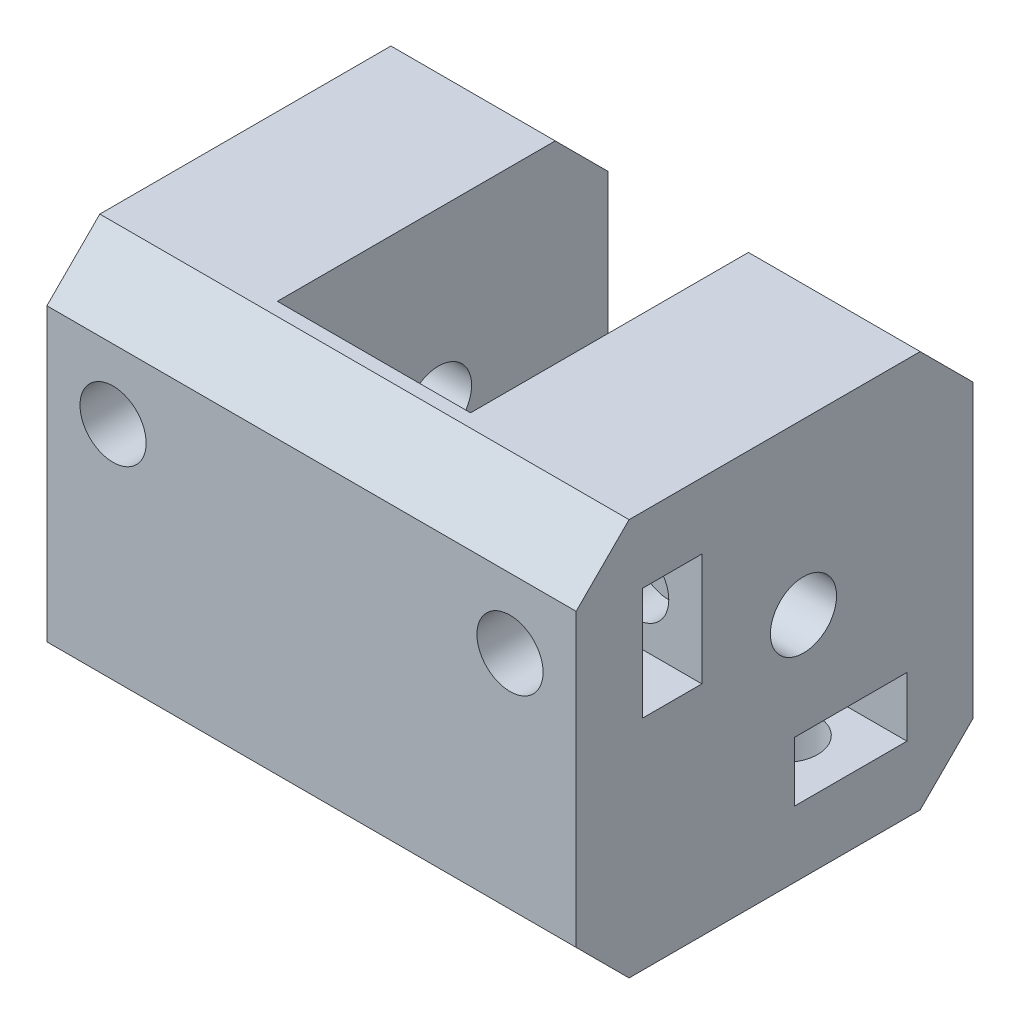
SolidWorks part; units mm, degrees
ref_plane "Front Plane" through (0, 0, 0) normal (0, 0, 1) x (1, 0, 0)
ref_plane "Top Plane" through (0, 0, 0) normal (0, 1, 0) x (1, 0, 0)
ref_plane "Right Plane" through (0, 0, 0) normal (1, 0, 0) x (0, 0, -1)
sketch "Sketch1" plane through (0, 0, 0) normal (0, 0, 1) x (1, 0, 0)
  line L0 (-71.5929, 28.752) -> (-71.5929, 34.452) construction
  line L1 (-31.5929, 27.752) -> (-71.5929, 27.752)
  line L2 (-31.5929, 27.752) -> (-31.5929, 57.752)
  line L3 (-31.5929, 57.752) -> (-71.5929, 57.752)
  line L4 (-71.5929, 27.752) -> (-71.5929, 57.752)
  line L5 (-64.8929, 27.752) -> (-70.5929, 27.752) construction
  line L6 (-31.5929, 34.452) -> (-31.5929, 28.752) construction
  dimension "D1" = 30
extrude "Boss-Extrude1" add sketch "Sketch1" along normal blind 30 contours L3 L4 L1 L2
sketch "Sketch2" plane through (0, 57.752, 0) normal (0, 1, 0) x (1, 0, 0)
  line L0 (-31.5929, 0) -> (-71.5929, 0) construction
  line L1 (-44.5729, -25) -> (-59.1729, -25)
  line L2 (-44.5729, -25) -> (-44.5729, 8.7289)
  line L3 (-44.5729, 8.7289) -> (-59.1729, 8.7289)
  line L4 (-59.1729, -25) -> (-59.1729, 8.7289)
  line L6 (-45.5729, -15.5089) -> (-45.5729, -10.5089) construction
  line L8 (-58.1729, -6.0089) -> (-58.1729, -20.0089) construction
  dimension "D1" = 25
  dimension "D2" = 1
  dimension "D3" = 1
extrude "Cut-Extrude1" cut sketch "Sketch2" against normal offset from surface (25 mm away) 5 up to face at (-51.5929, 27.752, 15)
sketch "Sketch3" plane through (-31.5929, 0, 0) normal (1, 0, 0) x (0, 0, -1)
  line L0 (0, 57.752) -> (-30, 27.752) construction
  line L1 (-30, 57.752) -> (0, 57.752) construction
  line L2 (0, 27.752) -> (0, 57.752) construction
  circle A1 centre (-12.8221, 44.9299) radius 2.5 construction
  circle A2 centre (-12.8221, 44.9299) radius 2.5
  dimension "D1" = 5
extrude "Cut-Extrude2" cut sketch "Sketch3" against normal through all contours A2
sketch "Sketch4" plane through (-31.5929, 0, 0) normal (1, 0, 0) x (0, 0, -1)
  line L0 (0, 57.752) -> (-30, 27.752) construction
  line L1 (-5, 32.752) -> (-13.5, 32.752)
  line L2 (-5, 32.752) -> (-5, 37.252)
  line L3 (-5, 37.252) -> (-13.5, 37.252)
  line L4 (-13.5, 32.752) -> (-13.5, 37.252)
  line L5 (-25, 52.752) -> (-25, 44.252)
  line L6 (-25, 52.752) -> (-20.5, 52.752)
  line L7 (-20.5, 52.752) -> (-20.5, 44.252)
  line L8 (-25, 44.252) -> (-20.5, 44.252)
  line L9 (0, 27.752) -> (0, 57.752) construction
  line L10 (-30, 27.752) -> (0, 27.752) construction
  dimension "D1" = 8.5
  dimension "D2" = 4.5
  dimension "D3" = 5
  dimension "D4" = 5
extrude "Cut-Extrude3" cut sketch "Sketch4" against normal blind 9
extrude "Cut-Extrude4" cut sketch "Sketch4<2>" along normal blind 9 from surface starting at face at (-71.5929, 44.9299, 10.3221)
sketch "Sketch4<2>" plane through (-31.5929, 0, 0) normal (1, 0, 0) x (0, 0, -1) same geometry as "Sketch4"
sketch "Sketch5" plane through (0, 0, 30) normal (0, 0, 1) x (1, 0, 0)
  line L0 (-62.5929, 44.252) -> (-62.5929, 52.752) construction
  line L1 (-40.5929, 52.752) -> (-40.5929, 44.252) construction
  line L2 (-62.5929, 44.252) -> (-62.5929, 52.752) construction
  line L3 (-40.5929, 52.752) -> (-40.5929, 44.252) construction
  line L4 (-66.5929, 48.502) -> (-36.5929, 48.502) construction
  circle A0 centre (-66.5929, 48.502) radius 2.5
  circle A1 centre (-36.5929, 48.502) radius 2.5
  point P8 (-62.5929, 48.502)
  dimension "D3" = 5
  dimension "D1" = 4
  dimension "D2" = 4
extrude "Cut-Extrude5" cut sketch "Sketch5" against normal blind 12
ref_plane "Plane1" through (0, 28.876, 28.876) normal (0, -0.7071, -0.7071) x (-1, 0, 0)
mirror "Mirror1" about plane through (0, 28.876, 28.876) normal (0, -0.7071, -0.7071) of "Cut-Extrude5"
chamfer "Chamfer1" distance 4 angle 45 5 edges at (-51.5929, 57.752, 30) (-65.3829, 57.752, 0) (-38.0829, 57.752, 0) (-51.5929, 27.752, 0) (-51.5929, 27.752, 30)
